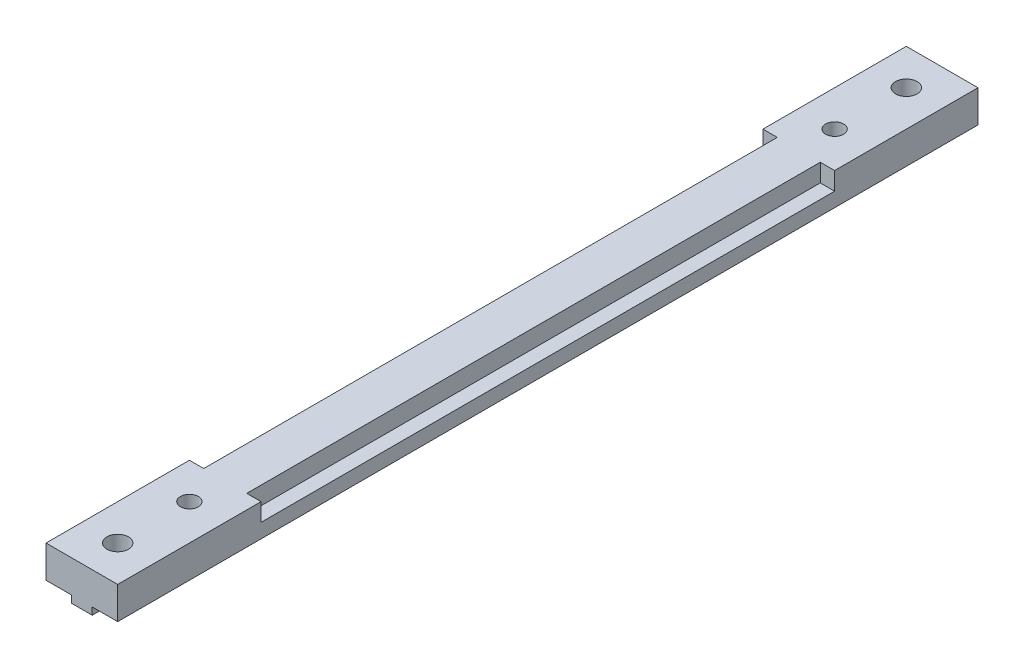
SolidWorks part; units mm, degrees
ref_plane "Front Plane" through (0, 0, 0) normal (0, 0, 1) x (1, 0, 0)
ref_plane "Top Plane" through (0, 0, 0) normal (0, 1, 0) x (1, 0, 0)
ref_plane "Right Plane" through (0, 0, 0) normal (1, 0, 0) x (0, 0, -1)
sketch "Sketch1" plane through (0, 0, 0) normal (0, 0, 1) x (1, 0, 0)
  line L0 (-5, 0) -> (5, 0)
  line L1 (5, 0) -> (5, -4.5)
  line L2 (5, -4.5) -> (1.45, -4.5)
  line L3 (1.45, -4.5) -> (1.45, -5.5)
  line L4 (1.45, -5.5) -> (-1.45, -5.5)
  line L5 (-1.45, -5.5) -> (-1.45, -4.5)
  line L6 (-1.45, -4.5) -> (-5, -4.5)
  line L7 (-5, -4.5) -> (-5, 0)
  point P9 (0, 0)
  dimension "D1" = 10
  dimension "D2" = 4.5
  dimension "D3" = 1
  dimension "D4" = 2.9
extrude "Main" add sketch "Sketch1" along normal blind 120
sketch "Sketch2" plane through (0, 0, 0) normal (0, 1, 0) x (1, 0, 0)
  line L0 (5, -120) -> (-5, -120) construction
  line L1 (5, 0) -> (-5, 0) construction
  circle A0 centre (0, -105) radius 1.25
  circle A1 centre (0, -15) radius 1.25
  circle A2 centre (0, -5) radius 1.5
  circle A3 centre (0, -115) radius 1.5
  point P13 (0, 0)
  dimension "D1" = 2.5
  dimension "D4" = 3
  dimension "D2" = 15
  dimension "D3" = 90
  dimension "D5" = 5
  dimension "D6" = 5
extrude "MainHoles" cut sketch "Sketch2" against normal through all
sketch "Sketch3" plane through (0, 0, 0) normal (0, 1, 0) x (1, 0, 0)
  line L0 (-5, -120) -> (-5, 0) construction
  line L1 (-5, -20) -> (-3, -20)
  line L2 (-5, -20) -> (-5, -100)
  line L3 (-5, -100) -> (-3, -100)
  line L4 (-3, -20) -> (-3, -100)
  line L5 (5, -120) -> (5, 0) construction
  line L6 (3, -20) -> (5, -20)
  line L7 (3, -20) -> (3, -100)
  line L8 (3, -100) -> (5, -100)
  line L9 (5, -20) -> (5, -100)
  line L10 (5, -120) -> (-5, -120) construction
  dimension "D1" = 6
  dimension "D2" = 80
  dimension "D3" = 20
extrude "PinHoles" cut sketch "Sketch3" against normal blind 2.5
